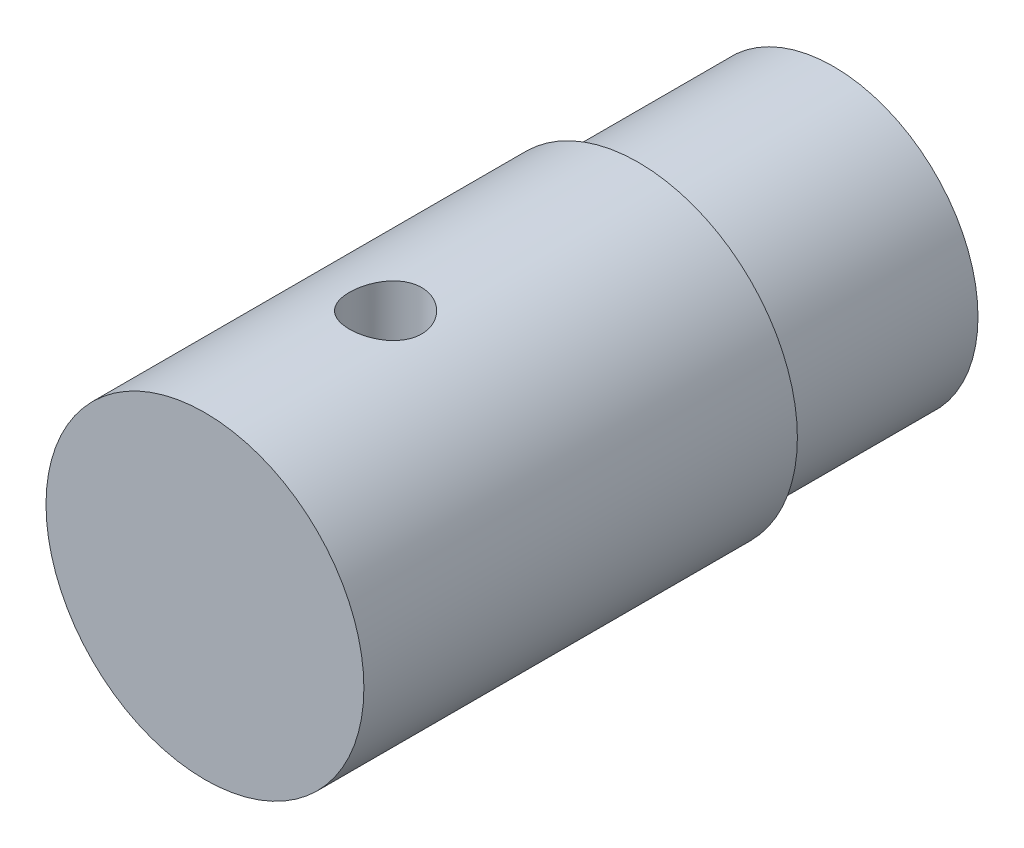
SolidWorks part; units mm, degrees
ref_plane "Front Plane" through (0, 0, 0) normal (0, 0, 1) x (1, 0, 0)
ref_plane "Top Plane" through (0, 0, 0) normal (0, 1, 0) x (1, 0, 0)
ref_plane "Right Plane" through (0, 0, 0) normal (1, 0, 0) x (0, 0, -1)
sketch "Sketch1" plane through (0, 0, 0) normal (0, 0, 1) x (1, 0, 0)
  circle A0 centre (0, 0) radius 10
  dimension "D1" = 20
extrude "Boss-Extrude1" add sketch "Sketch1" along normal blind 13.5
sketch "Sketch2" plane through (0, 0, 13.5) normal (0, 0, 1) x (1, 0, 0)
  circle A0 centre (0, 0) radius 11
  dimension "D1" = 22
extrude "Boss-Extrude2" add sketch "Sketch2" along normal blind 30
sketch "Sketch5" plane through (0, 0, 0) normal (0, 1, 0) x (1, 0, 0)
  line L0 (-11, -43.5) -> (11, -43.5) construction
  line L1 (0, -31) -> (0, 0) construction
  circle A0 centre (0, -31) radius 2.5
  dimension "D1" = 5
  dimension "D2" = 12.5
extrude "Cut-Extrude3" cut sketch "Sketch5" against normal through all both and the other way through all
sketch "Sketch6" plane through (0, 0, 0) normal (0, 1, 0) x (1, 0, 0)
  circle A0 centre (0, -31) radius 2.5 construction
  circle A1 centre (0, -31) radius 2.5
  circle A2 centre (0, -31) radius 2
  dimension "D1" = 4
extrude "Boss-Extrude3" add sketch "Sketch6" along normal mid plane 12
sketch "Sketch7" plane through (0, 0, 0) normal (0, 0, -1) x (-1, 0, 0)
  line L0 (0, 3) -> (0, 4)
  line L1 (-1, 4) -> (1, 4)
  line L2 (1, 4) -> (1, 2.8284)
  line L3 (-1, 4) -> (-1, 2.8284)
  circle A0 centre (0, 0) radius 3
  point P8 (0, 4)
  dimension "D1" = 6
  dimension "D2" = 1
  dimension "D3" = 2
extrude "Cut-Extrude4" cut sketch "Sketch7" against normal blind 25 contours A0 | A0 L2 L1 L0 | A0 L0 L1 L3 region at (0.5135, 3.4705, 0) region at (-0.5135, 3.4705, 0) region at (0, 0, 0)
hole_wizard "Tap Drill for M3 Tap1" positions "Sketch8" profile "Sketch9" hole size "M3" standard "DIN"
sketch "Sketch8" plane through (0, 0, 0) normal (0, 0, -1) x (-1, 0, 0)
  line L0 (0, 0) -> (-5.9811, 5.9811) construction
  line L2 (0, 0) -> (-6.099, 0) construction
  circle A0 centre (0, 0) radius 7.5 construction
  point P13 (-5.3033, 5.3033)
  point P19 (5.3033, 5.3033)
  point P20 (5.3033, -5.3033)
  point P21 (-5.3033, -5.3033)
  dimension "D2" = 15
  dimension "D1" = 45
  dimension "D3" = 4
sketch "Sketch9" plane through (5.3033, -5.3033, 0) normal (1, 0, 0) x (0, 1, 0)
  line L0 (0, 0) -> (0, 25.7511)
  line L1 (0, 25.7511) -> (1.25, 25)
  line L2 (1.25, 25) -> (1.25, 0)
  line L5 (1.25, 0) -> (0, 0)
  line L10 (0, 25.7511) -> (-1.25, 25) construction
  line L11 (0, -6.35) -> (0, 107.95) construction
  dimension "Hole Dia." = 2.5
  dimension "Hole Depth" = 25
  dimension "Drill Angle" = 118
